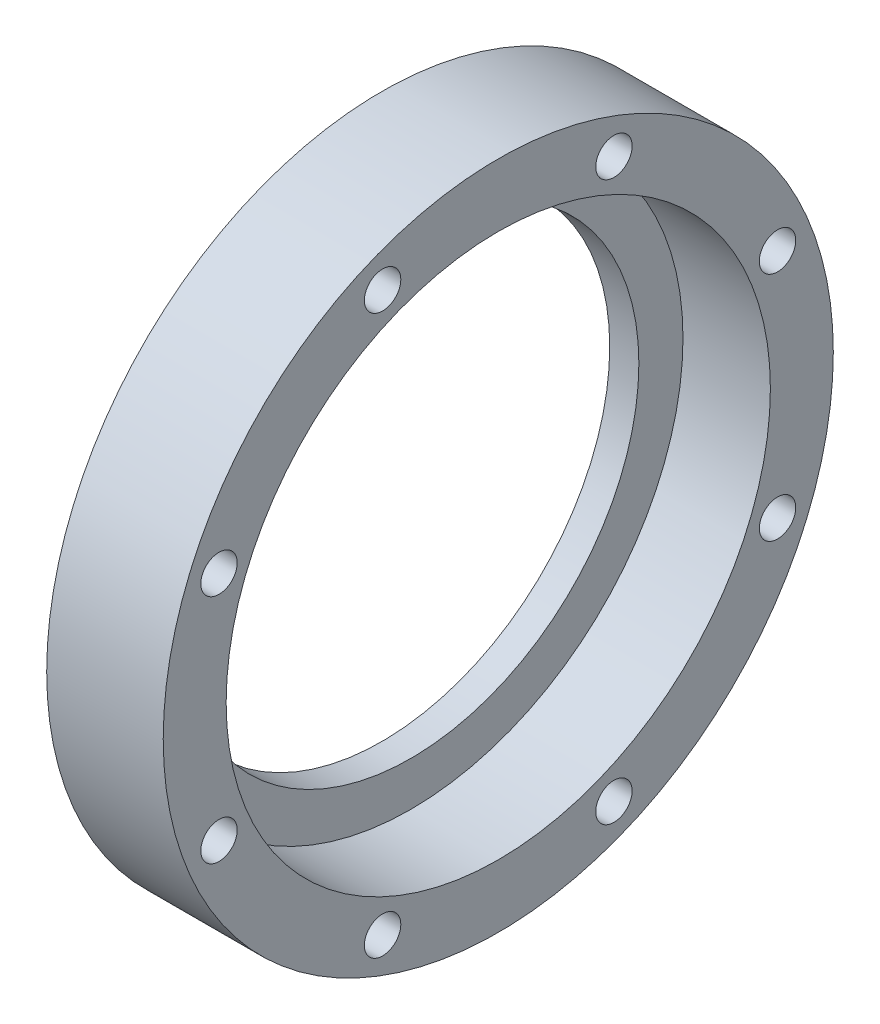
SolidWorks part; units mm, degrees
material "3d打印 35%"
ref_plane "前视基准面" through (0, 0, 0) normal (0, 0, 1) x (1, 0, 0)
ref_plane "上视基准面" through (0, 0, 0) normal (0, 1, 0) x (1, 0, 0)
ref_plane "右视基准面" through (0, 0, 0) normal (1, 0, 0) x (0, 0, -1)
other "Configuration Table"
sketch "草图1" plane through (0, 0, 0) normal (1, 0, 0) x (0, 0, -1)
  line L0 (0, 0) -> (0, 43.0868) construction
  line L1 (0, 0) -> (13.8083, 33.3362) construction
  circle A0 centre (0, 0) radius 23
  circle A1 centre (0, 0) radius 21.6522 construction
  circle A2 centre (0, 0) radius 15.6522
  circle A3 centre (0, 0) radius 18.68
  circle A4 centre (7.9407, 19.1705) radius 1.25
  circle A5 centre (19.1705, 7.9407) radius 1.25
  circle A6 centre (19.1705, -7.9407) radius 1.25
  circle A7 centre (7.9407, -19.1705) radius 1.25
  circle A8 centre (-7.9407, -19.1705) radius 1.25
  circle A9 centre (-19.1705, -7.9407) radius 1.25
  circle A10 centre (-19.1705, 7.9407) radius 1.25
  circle A11 centre (-7.9407, 19.1705) radius 1.25
  point P27 (0, 0)
  dimension "D1" = 8
  dimension "D2" = 46
  dimension "D3" = 2.5
  dimension "D4" = 2.5
  dimension "D5" = 2.5
  dimension "D6" = 20.75
  dimension "D7" = 37.36
  dimension "D8" = 46
extrude "凸台-拉伸2" add sketch "草图1" along normal blind 2 contours A3 A2 region at (0, 0, 18.1516)
extrude "凸台-拉伸3" add sketch "草图1<4>" along normal blind 8 contours A0 A11 A10 A9 A8 A7 A6 A5 A4 A3 region at (0, 0, 22.3495)
sketch "草图1<4>" plane through (0, 0, 0) normal (1, 0, 0) x (0, 0, -1) same geometry as "草图1"
